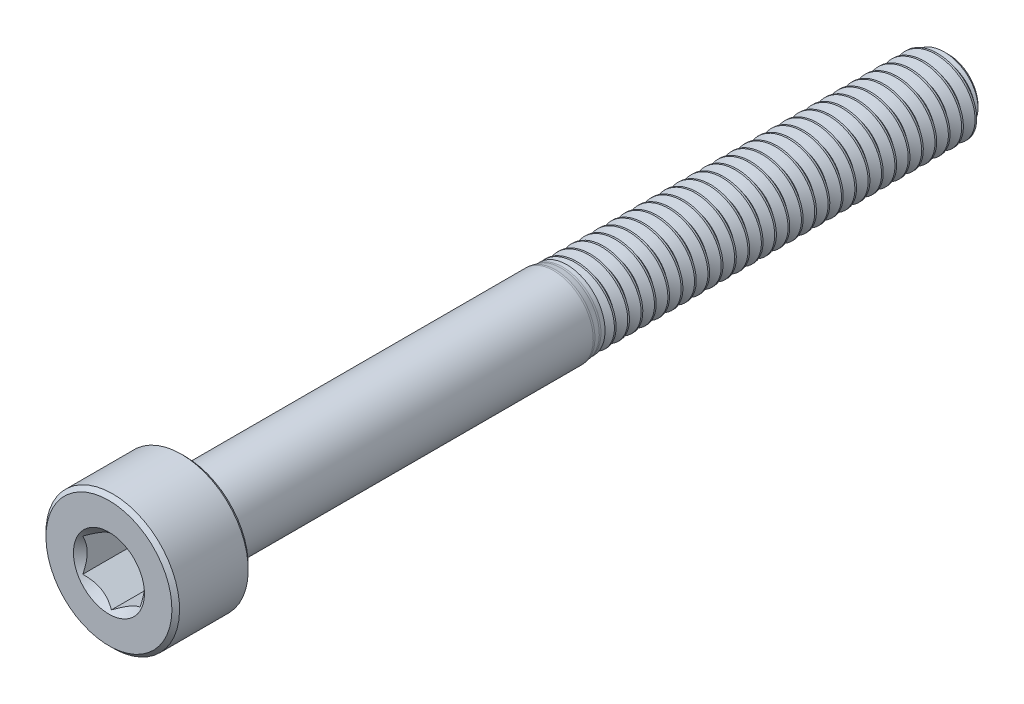
SolidWorks part; units mm, degrees
ref_plane "Front Plane" through (0, 0, 0) normal (0, 0, 1) x (1, 0, 0)
ref_plane "Top Plane" through (0, 0, 0) normal (0, 1, 0) x (1, 0, 0)
ref_plane "Right Plane" through (0, 0, 0) normal (1, 0, 0) x (0, 0, -1)
sketch "Sketch1" plane through (0, 0, 0) normal (1, 0, 0) x (0, 0, -1)
  line L0 (-22, 0) -> (22, 0) construction
  line L1 (22, 0) -> (22, 1.5453) construction
  line L2 (22, 1.5453) -> (21.5453, 2) construction
  line L3 (21.5453, 2) -> (21.475, 2) construction
  line L4 (21.475, 2) -> (-18, 2) construction
  line L5 (-18, 2) -> (-18, 3.5) construction
  line L6 (-18, 3.5) -> (-22, 3.5) construction
  line L7 (-22, 3.5) -> (-22, 0) construction
  line L8 (22, 1.5453) -> (22, 2) construction
  line L9 (21.9563, 2.0758) -> (22.3062, 1.4696) construction
  line L10 (22.3062, 1.4696) -> (22.6562, 2.0758) construction
  line L11 (22.6562, 2.0758) -> (21.9563, 2.0758) construction
  line L12 (22.3062, 2.0758) -> (22.3062, 2) construction
  line L13 (22.3062, 1.4696) -> (22.3062, 1.5453) construction
  line L14 (22.2625, 1.5453) -> (22.35, 1.5453) construction
  line L15 (22, 2) -> (22.6125, 2) construction
  line L16 (21.9781, 2.0379) -> (22.6344, 2.0379) construction
  line L17 (22, 0) -> (22, -2) construction
  line L18 (-18.2, 3.5) -> (-18, 3.3) construction
  line L19 (-21.8, 3.5) -> (-22, 3.3) construction
  line L20 (-18, 2) -> (-18, 0) construction
  line L21 (-18, 1) -> (-4.6667, 1) construction
  line L22 (-4.6667, 1) -> (8.6667, 1) construction
  line L23 (8.6667, 1) -> (22, 1) construction
  line L24 (-4.6667, 1) -> (-4.6667, 2) construction
  line L25 (-4.6667, 2) -> (-4.6667, 3.5) construction
  line L26 (8.6667, 1) -> (8.6667, 3.5) construction
  point P0 (-22, 1.5)
  point P3 (20.25, 2)
  point P4 (0, 0)
  point P18 (8.6667, 2)
  point P22 (22.3062, 1.5453)
  point P24 (21.475, 2)
  point P25 (22.3062, 2)
  point P28 (22.3062, 2.0379)
  point P29 (20.25, -2)
  point P30 (-4.6667, 2)
  point P31 (-20, 3.5)
  point P37 (-18.7, 3.5)
  point P38 (-21.7, 3.5)
  point P45 (-4.6667, 1)
  point P46 (8.6667, 1)
  point P49 (2, 2)
  dimension "D1" = 45
  dimension "D2" = 0.0875
  dimension "D7" = 0.2
  dimension "D8" = 0.2
  dimension "D9" = 0.2
  dimension "D10" = 0.1
  dimension "D11" = 0.5
  dimension "Drive Size" = 3
  dimension "Head Diameter" = 7
  dimension "Head Height" = 4
  dimension "Thread Pitch" = 0.7
  dimension "Thread Dia" = 4
  dimension "Length" = 40
  dimension "D12" = 0.525
  dimension "D4" = 1.75
  dimension "Minimum Thread Length" = 20
  dimension "D3" = 20
sketch "Sketch2" plane through (0, 0, 0) normal (1, 0, 0) x (0, 0, -1)
  line L0 (-22, 0) -> (-22, 3.3)
  line L1 (-21.8, 3.5) -> (-18.2, 3.5)
  line L2 (-18, 3.3) -> (-18, 2.2758)
  line L4 (21.5453, 2) -> (22, 1.5453)
  line L5 (22, 1.5453) -> (22, 0)
  line L6 (-18, 3.5) -> (-22, 3.5) construction
  line L7 (22, 0) -> (-22, 0)
  line L8 (-21.8, 3.5) -> (-22, 3.3) construction
  line L10 (-21.8, 3.5) -> (-22, 3.3)
  line L14 (-18.2, 3.5) -> (-18, 3.3) construction
  line L16 (-18.2, 3.5) -> (-18, 3.3)
  line L17 (-18, 2) -> (-18, 3.5) construction
  line L18 (-17.8, 2.0758) -> (1.3073, 2.0758)
  line L19 (1.7867, 2) -> (21.5453, 2)
  line L20 (21.475, 2) -> (-18, 2) construction
  line L21 (1.4048, 2.0662) -> (1.6892, 2.0096)
  line L22 (22.6562, 2.0758) -> (21.9563, 2.0758) construction
  arc A1 (-18, 2.2758) -> (-17.8, 2.0758) centre (-17.8, 2.2758) ccw
  arc A2 (1.3073, 2.0758) -> (1.4048, 2.0662) centre (1.3073, 1.5758) cw
  arc A3 (1.6892, 2.0096) -> (1.7867, 2) centre (1.7867, 2.5) ccw
  point P39 (1.7375, 2)
  dimension "D3" = 0.2
  dimension "D6" = 0.5
  dimension "D4" = 11.25
  dimension "D5" = 0.2625
revolve "Revolve1" add sketch "Sketch2" angle 360 about L7
sketch "Sketch3" plane through (0, 0, 22) normal (0, 0, 1) x (1, 0, 0)
  line L1 (1.5, -0.866) -> (1.5, 0.866)
  line L2 (1.5, 0.866) -> (0, 1.7321)
  line L3 (0, 1.7321) -> (-1.5, 0.866)
  line L4 (-1.5, 0.866) -> (-1.5, -0.866)
  line L5 (-1.5, -0.866) -> (0, -1.7321)
  line L6 (0, -1.7321) -> (1.5, -0.866)
  circle A0 centre (0, 0) radius 1.5 construction
  circle A1 centre (0, 0) radius 3.5 construction
  circle A2 centre (0, 0) radius 3.5 construction
  circle A3 centre (0, 0) radius 1.7321 construction
  dimension "D1" = 3.4641
extrude "Cut-Extrude1" cut sketch "Sketch3" against normal offset from surface (3 mm away) 1 up to face at (0, 3.3, 18)
sketch "Sketch4" plane through (0, 0, 22) normal (0, 0, 1) x (1, 0, 0)
  circle A0 centre (0, 0) radius 1.862
  dimension "D1" = 3.7239
extrude "Cut-Extrude2" cut sketch "Sketch4" against normal up to vertex (2 mm away) draft 45 up to point (0, 3.5, 20)
sketch "Sketch11" plane through (0, 0, 0) normal (1, 0, 0) x (0, 0, -1)
  line L0 (-22, 0) -> (22, 0) construction
  line L1 (-22, 0) -> (22, 0) construction
  line L2 (-15.5, 0) -> (-15.5, 2) construction
  line L3 (21.475, 2) -> (-18, 2) construction
  line L4 (-1.1927, 0) -> (-1.1927, 2) construction
  point P2 (-15.5, 0)
  point P3 (-1.1927, 0)
  dimension "D1" = 2.5
  dimension "D2" = 2.5
sketch "Sketch6" plane through (0, 0, -22) normal (0, 0, -1) x (-1, 0, 0)
  circle A0 centre (0, 0) radius 2
curve "Helix/Spiral1" pitch 0.7 height 20.7 radius 2 centre (0, 0, -22) axis (0, 0, 1) start towards (0, 1, 0)
sketch "Sketch10" plane through (0, 0, 0) normal (1, 0, 0) x (0, 0, -1)
  line L0 (2, -2) -> (2, 2)
  line L2 (-22, 0) -> (22, 0) construction
  point P3 (2, 0)
split "Split1" trim tools "Sketch10" bodies to split 106 resulting bodies 114 115
sketch "Sketch7" plane through (0, 0, 0) normal (1, 0, 0) x (0, 0, -1)
  line L0 (21.9781, 2.0379) -> (22.6344, 2.0379)
  line L1 (22.6344, 2.0379) -> (22.35, 1.5453)
  line L2 (22.35, 1.5453) -> (22.2625, 1.5453)
  line L3 (22.2625, 1.5453) -> (21.9781, 2.0379)
sweep "Cut-Sweep1" cut profiles "Sketch7" path "Helix/Spiral1" align with end faces yes
sketch "Sketch8" plane through (0, 0, 0) normal (1, 0, 0) x (0, 0, -1)
  line L0 (-18, 0) -> (-18, 2)
  line L2 (-18, 2) -> (2, 2)
  line L4 (2, 2) -> (3.1547, 0)
  line L5 (3.1547, 0) -> (-18, 0)
  line L6 (21.475, 2) -> (-18, 2) construction
  line L7 (-22, 0) -> (22, 0) construction
  dimension "D1" = 60
  dimension "D2" = 20
revolve "Revolve2" add sketch "Sketch8" angle 360 about L5
equation "\"D2@Sketch1\" = \"Thread Pitch@Sketch1\" / 8"
equation "\"D4@Helix/Spiral1\" = \"Thread Pitch@Sketch1\""
equation "\"D7@Sketch1\" = \"Head Height@Sketch1\" * .05"
equation "\"D8@Sketch1\"=\"D7@Sketch1\""
equation "\"D9@Sketch1\"=\"D7@Sketch1\""
equation "\"D10@Sketch1\"=\"D7@Sketch1\"/2"
equation "\"D11@Sketch1\"=\"D10@Sketch1\"*5"
equation "\"D4@Sketch1\"=\"Thread Pitch@Sketch1\"*2.5"
equation "\"D12@Sketch1\"=\"Thread Pitch@Sketch1\"*.75"
equation "\"D3@Helix/Spiral1\"=\"Minimum Thread Length@Sketch1\"+\"Thread Pitch@Sketch1\""
equation "\"D2@Sketch8\"=\"Minimum Thread Length@Sketch1\""
equation "\"D3@Sketch2\"=\"Thread Dia@Sketch1\"*0.05"
equation "\"D5@Sketch2\"=\"D12@Sketch1\"*0.5"
equation "\"D6@Sketch2\"=\"Thread Dia@Sketch1\"*0.125"
equation "\"D1@Sketch11\"=\"D3@Sketch1\"*0.125"
equation "\"D2@Sketch11\"=\"D1@Sketch11\""
equation "\"D1@Sketch4\"=\"D1@Sketch3\"*1.075"
